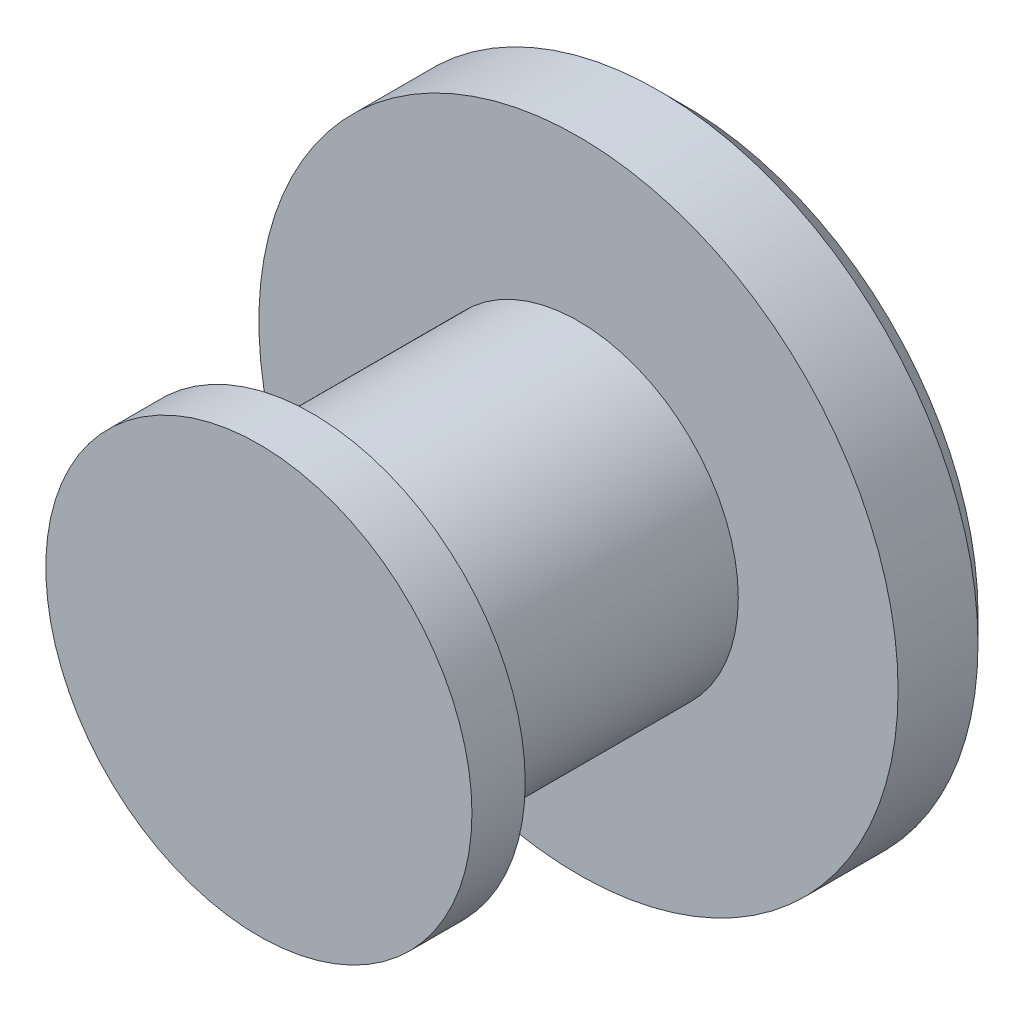
SolidWorks part; units mm, degrees
material "Alloy Steel"
ref_plane "Front Plane" through (0, 0, 0) normal (0, 0, 1) x (1, 0, 0)
ref_plane "Top Plane" through (0, 0, 0) normal (0, 1, 0) x (1, 0, 0)
ref_plane "Right Plane" through (0, 0, 0) normal (1, 0, 0) x (0, 0, -1)
sketch "Sketch1" plane through (0, 0, 0) normal (0, 0, 1) x (1, 0, 0)
  circle A0 centre (0, 0) radius 6
  circle A1 centre (0, 0) radius 4
  circle A2 centre (0, 0) radius 3
  dimension "D1" = 12
  dimension "D2" = 6
  dimension "D3" = 8
extrude "Boss-Extrude1" add sketch "Sketch1" along normal blind 5 contours A2 region at (0, 0, 0)
extrude "Boss-Extrude2" add sketch "Sketch1<3>" along normal blind 1 from surface contours A1 A2 | A2 region at (-3.8869, 0, 0) region at (0, 0, 0) starting at face at (3, 0, 5)
sketch "Sketch1<3>" plane through (0, 0, 0) normal (0, 0, 1) x (1, 0, 0) same geometry as "Sketch1"
extrude "Boss-Extrude3" add sketch "Sketch1<4>" against normal blind 2 contours A0 A1 | A1 A2 | A2 region at (-5.8303, 0, 0) region at (-3.8869, 0, 0) region at (0, 0, 0)
sketch "Sketch1<4>" plane through (0, 0, 0) normal (0, 0, 1) x (1, 0, 0) same geometry as "Sketch1"
chamfer "Chamfer1" distance 0.5 angle 45 1 edges at (6, 0, -2)
